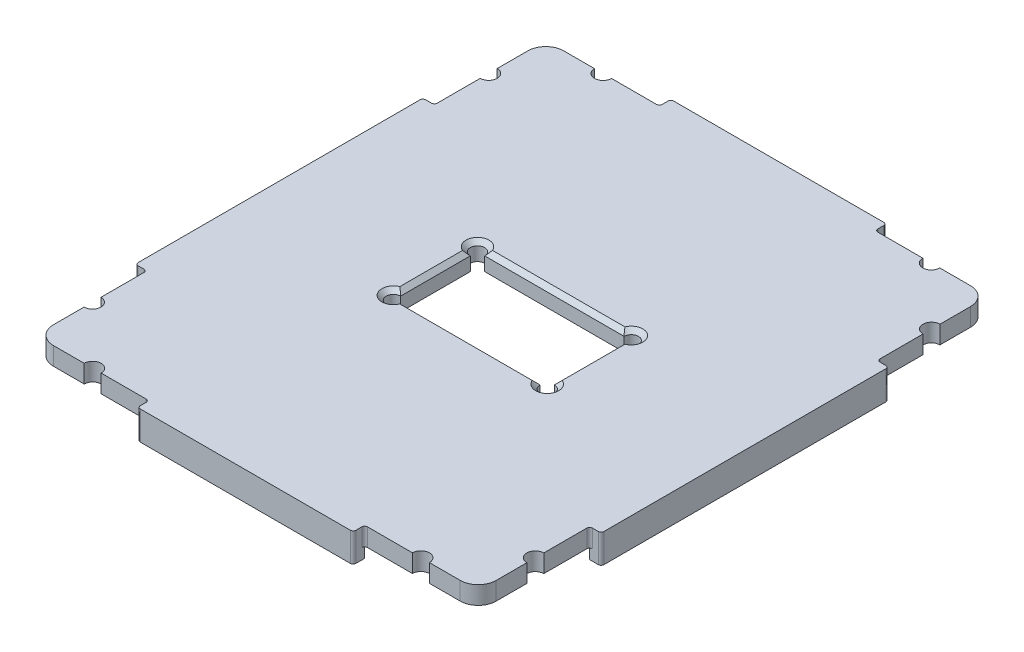
SolidWorks part; units mm, degrees
ref_plane "Front Plane" through (0, 0, 0) normal (0, 0, 1) x (1, 0, 0)
ref_plane "Top Plane" through (0, 0, 0) normal (0, 1, 0) x (1, 0, 0)
ref_plane "Right Plane" through (0, 0, 0) normal (1, 0, 0) x (0, 0, -1)
sketch "Sketch1" plane through (0, 0, 0) normal (0, 1, 0) x (1, 0, 0)
  line L1 (-39.116, 45.085) -> (39.116, 45.085)
  line L2 (-39.116, 45.085) -> (-39.116, -45.085)
  line L3 (-39.116, -45.085) -> (39.116, -45.085)
  line L4 (39.116, 45.085) -> (39.116, -45.085)
  line L5 (-12.319, 7.493) -> (12.319, 7.493)
  line L6 (-13.589, 6.223) -> (-13.589, -6.096)
  line L7 (-12.319, -7.366) -> (12.319, -7.366)
  line L8 (13.589, 6.223) -> (13.589, -6.096)
  arc A0 (-12.319, 7.493) -> (-13.589, 6.223) centre (-13.589, 7.493) ccw
  arc A1 (13.589, 6.223) -> (12.319, 7.493) centre (13.589, 7.493) ccw
  arc A2 (12.319, -7.366) -> (13.589, -6.096) centre (13.589, -7.366) ccw
  arc A3 (-13.589, -6.096) -> (-12.319, -7.366) centre (-13.589, -7.366) ccw
  dimension "D9" = 2.54
  dimension "D10" = 2.54
  dimension "D11" = 2.54
  dimension "D12" = 2.54
  dimension "D1" = 78.232
  dimension "D2" = 90.17
  dimension "D3" = 39.116
  dimension "D4" = 45.085
  dimension "D5" = 27.178
  dimension "D6" = 13.589
  dimension "D7" = 14.859
  dimension "D8" = 7.366
  dimension "D13" = 12.319
  dimension "D14" = 12.319
  dimension "D15" = 24.638
extrude "Boss-Extrude1" add sketch "Sketch1" along normal blind 3.175
fillet "Fillet1" radius 3.175 4 edges at (-39.116, 1.5875, -45.085) (39.116, 1.5875, -45.085) (39.116, 1.5875, 45.085) (-39.116, 1.5875, 45.085)
sketch "Sketch2" plane through (0, 3.175, 0) normal (0, 1, 0) x (1, 0, 0)
  line L0 (19.05, -47.117) -> (19.05, -45.085)
  line L1 (-39.116, 41.91) -> (-39.116, -41.91) construction
  line L2 (-41.148, 25.4) -> (-39.116, 25.4)
  line L3 (-41.148, 25.4) -> (-41.148, -25.4)
  line L4 (-41.148, -25.4) -> (-39.116, -25.4)
  line L5 (-39.116, 25.4) -> (-39.116, -25.4)
  line L6 (0, 45.085) -> (0, -45.085) construction
  line L7 (35.941, 45.085) -> (-35.941, 45.085) construction
  line L8 (-35.941, -45.085) -> (35.941, -45.085) construction
  line L9 (-39.116, 0) -> (39, 0) construction
  line L10 (-19.05, 47.117) -> (19.05, 47.117)
  line L11 (-19.05, 47.117) -> (-19.05, 45.085)
  line L12 (39.116, 25.4) -> (39.116, -25.4)
  line L13 (41.148, -25.4) -> (39.116, -25.4)
  line L14 (41.148, 25.4) -> (41.148, -25.4)
  line L15 (41.148, 25.4) -> (39.116, 25.4)
  line L16 (-19.05, 45.085) -> (19.05, 45.085)
  line L17 (19.05, 47.117) -> (19.05, 45.085)
  line L18 (-19.05, -45.085) -> (19.05, -45.085)
  line L19 (-19.05, -47.117) -> (-19.05, -45.085)
  line L20 (-19.05, -47.117) -> (19.05, -47.117)
  point P4 (-39.116, 0)
  dimension "D1" = 50.8
  dimension "D2" = 2.032
  dimension "D3" = 25.4
  dimension "D9" = 19.05
  dimension "D10" = 38.1
  dimension "D12" = 2.032
extrude "Boss-Extrude2" add sketch "Sketch2" against normal blind 5.08
fillet "Fillet3" radius 0.508 16 edges at (-39.116, 1.5875, 25.4) (-41.148, 0.635, 25.4) (-41.148, 0.635, -25.4) (-39.116, 1.5875, -25.4) (-19.05, 0.635, -47.117) (-19.05, 1.5875, -45.085) (19.05, 0.635, -47.117) (19.05, 1.5875, -45.085) (39.116, 1.5875, -25.4) (41.148, 0.635, -25.4) (41.148, 0.635, 25.4) (39.116, 1.5875, 25.4) (19.05, 0.635, 47.117) (19.05, 1.5875, 45.085) (-19.05, 0.635, 47.117) (-19.05, 1.5875, 45.085)
sketch "Sketch3" plane through (0, 3.175, 0) normal (0, 1, 0) x (1, 0, 0)
  line L0 (-39.116, 41.91) -> (-39.116, 25.908) construction
  line L1 (-19.558, 45.085) -> (-35.941, 45.085) construction
  line L2 (-41.148, 24.892) -> (-41.148, -24.892) construction
  line L3 (18.542, 47.117) -> (-18.542, 47.117) construction
  line L4 (-41.148, 0) -> (41.148, 0) construction
  line L5 (41.148, -24.892) -> (41.148, 24.892) construction
  line L6 (0, 47.117) -> (0, -47.032) construction
  line L9 (-39.116, 36.5) -> (-39.116, 33.5)
  line L10 (-27.5, 45.085) -> (-30.5, 45.085)
  line L11 (27.5, 45.085) -> (30.5, 45.085)
  line L12 (39.116, 36.5) -> (39.116, 33.5)
  line L13 (39.116, -33.5) -> (39.116, -36.5)
  line L14 (30.5, -45.085) -> (27.5, -45.085)
  line L15 (-27.5, -45.085) -> (-30.5, -45.085)
  line L16 (-39.116, -36.5) -> (-39.116, -33.5)
  arc A0 (-39.116, 33.5) -> (-39.116, 36.5) centre (-39.116, 35) ccw
  arc A1 (-30.5, 45.085) -> (-27.5, 45.085) centre (-29, 45.085) ccw
  arc A2 (30.5, 45.085) -> (27.5, 45.085) centre (29, 45.085) cw
  arc A3 (39.116, 33.5) -> (39.116, 36.5) centre (39.116, 35) cw
  arc A4 (39.116, -33.5) -> (39.116, -36.5) centre (39.116, -35) ccw
  arc A5 (30.5, -45.085) -> (27.5, -45.085) centre (29, -45.085) ccw
  arc A6 (-30.5, -45.085) -> (-27.5, -45.085) centre (-29, -45.085) cw
  arc A7 (-39.116, -33.5) -> (-39.116, -36.5) centre (-39.116, -35) cw
  point P8 (-41.148, 0)
  point P11 (0, 47.117)
  dimension "D1" = 3
  dimension "D3" = 3
  dimension "D2" = 35
  dimension "D4" = 29
extrude "Cut-Extrude1" cut sketch "Sketch3" against normal through all
chamfer "Chamfer2" distance 0.762 angle 45 8 edges at (-14.487, 3.175, 8.264) (0, 3.175, 7.366) (14.487, 3.175, 8.264) (13.589, 3.175, -0.0635) (14.487, 3.175, -8.391) (-13.589, 3.175, -0.0635) (-14.487, 3.175, -8.391) (0, 3.175, -7.493)
